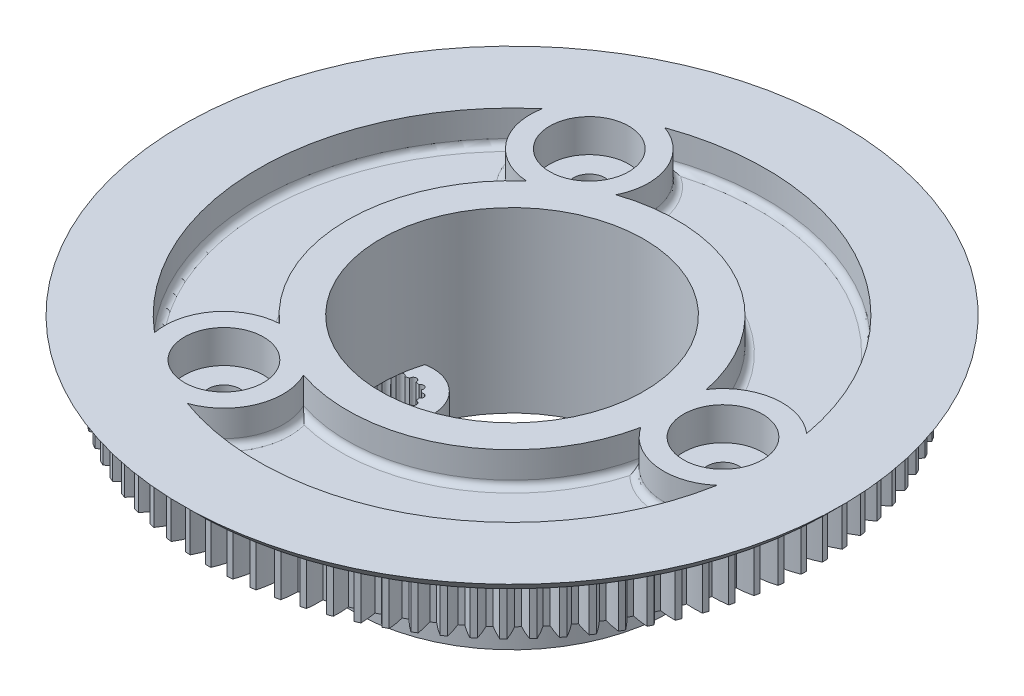
SolidWorks part; units mm, degrees
ref_plane "Plan de face" through (0, 0, 0) normal (0, 0, 1) x (1, 0, 0)
ref_plane "Plan de dessus" through (0, 0, 0) normal (0, 1, 0) x (1, 0, 0)
ref_plane "Plan de droite" through (0, 0, 0) normal (1, 0, 0) x (0, 0, -1)
sketch "Esquisse1" plane through (0, 0, 0) normal (0, 1, 0) x (1, 0, 0)
  arc A0 (22.9936, 0.5427) -> (22.9806, 0.9454) centre (0, 0) ccw
  arc A1 (22.8997, 2.1454) -> (22.8586, 2.5462) centre (0, 0) ccw
  arc A2 (22.6943, 3.7375) -> (22.6253, 4.1345) centre (0, 0) ccw
  arc A3 (22.3783, 5.3115) -> (22.2818, 5.7027) centre (0, 0) ccw
  arc A4 (21.9533, 6.8596) -> (21.8297, 7.2431) centre (0, 0) ccw
  arc A5 (21.4213, 8.3743) -> (21.2713, 8.7482) centre (0, 0) ccw
  arc A6 (20.7849, 9.8481) -> (20.6092, 10.2107) centre (0, 0) ccw
  arc A7 (20.0473, 11.274) -> (19.8468, 11.6235) centre (0, 0) ccw
  arc A8 (19.2121, 12.645) -> (18.9876, 12.9796) centre (0, 0) ccw
  arc A9 (18.2832, 13.9544) -> (18.0359, 14.2725) centre (0, 0) ccw
  arc A10 (17.2653, 15.1958) -> (16.9964, 15.4959) centre (0, 0) ccw
  arc A11 (16.1632, 16.3631) -> (15.8741, 16.6437) centre (0, 0) ccw
  arc A12 (14.9824, 17.4507) -> (14.6744, 17.7105) centre (0, 0) ccw
  arc A13 (13.7286, 18.4533) -> (13.4032, 18.691) centre (0, 0) ccw
  arc A14 (12.4079, 19.366) -> (12.0668, 19.5804) centre (0, 0) ccw
  arc A15 (11.0268, 20.1844) -> (10.6715, 20.3745) centre (0, 0) ccw
  arc A16 (9.5919, 20.9044) -> (9.2243, 21.0692) centre (0, 0) ccw
  arc A17 (8.1103, 21.5226) -> (7.7321, 21.6614) centre (0, 0) ccw
  arc A18 (6.5892, 22.0359) -> (6.2022, 22.148) centre (0, 0) ccw
  arc A19 (5.036, 22.4419) -> (4.6421, 22.5267) centre (0, 0) ccw
  arc A20 (3.4583, 22.7385) -> (3.0595, 22.7956) centre (0, 0) ccw
  arc A21 (1.8637, 22.9244) -> (1.4619, 22.9535) centre (0, 0) ccw
  arc A22 (0.2601, 22.9985) -> (-0.1429, 22.9996) centre (0, 0) ccw
  arc A23 (-1.3449, 22.9606) -> (-1.7469, 22.9336) centre (0, 0) ccw
  arc A24 (-2.9432, 22.8109) -> (-3.3424, 22.7558) centre (0, 0) ccw
  arc A25 (-4.5273, 22.55) -> (-4.9216, 22.4673) centre (0, 0) ccw
  arc A26 (-6.0893, 22.1793) -> (-6.4769, 22.0692) centre (0, 0) ccw
  arc A27 (-7.6216, 21.7005) -> (-8.0005, 21.5637) centre (0, 0) ccw
  arc A28 (-9.1168, 21.116) -> (-9.4853, 20.953) centre (0, 0) ccw
  arc A29 (-10.5675, 20.4286) -> (-10.9238, 20.2403) centre (0, 0) ccw
  arc A30 (-11.9668, 19.6417) -> (-12.3091, 19.429) centre (0, 0) ccw
  arc A31 (-13.3078, 18.7591) -> (-13.6344, 18.5231) centre (0, 0) ccw
  arc A32 (-14.584, 17.7851) -> (-14.8933, 17.5269) centre (0, 0) ccw
  arc A33 (-15.789, 16.7244) -> (-16.0796, 16.4453) centre (0, 0) ccw
  arc A34 (-16.9172, 15.5823) -> (-17.1876, 15.2835) centre (0, 0) ccw
  arc A35 (-17.963, 14.3642) -> (-18.2118, 14.0474) centre (0, 0) ccw
  arc A36 (-18.9212, 13.0762) -> (-19.1474, 12.7428) centre (0, 0) ccw
  arc A37 (-19.7873, 11.7245) -> (-19.9896, 11.3761) centre (0, 0) ccw
  arc A38 (-20.5569, 10.3156) -> (-20.7345, 9.9539) centre (0, 0) ccw
  arc A39 (-21.2264, 8.8565) -> (-21.3783, 8.4833) centre (0, 0) ccw
  arc A40 (-21.7925, 7.3543) -> (-21.918, 6.9714) centre (0, 0) ccw
  arc A41 (-22.2525, 5.8162) -> (-22.3509, 5.4255) centre (0, 0) ccw
  arc A42 (-22.604, 4.2498) -> (-22.6749, 3.8531) centre (0, 0) ccw
  arc A43 (-22.8454, 2.6626) -> (-22.8885, 2.262) centre (0, 0) ccw
  arc A44 (-22.9754, 1.0625) -> (-22.9905, 0.6599) centre (0, 0) ccw
  arc A45 (-22.9936, -0.5427) -> (-22.9806, -0.9454) centre (0, 0) ccw
  arc A46 (-22.8997, -2.1454) -> (-22.8586, -2.5462) centre (0, 0) ccw
  arc A47 (-22.6943, -3.7375) -> (-22.6253, -4.1345) centre (0, 0) ccw
  arc A48 (-22.3783, -5.3115) -> (-22.2818, -5.7027) centre (0, 0) ccw
  arc A49 (-21.9533, -6.8596) -> (-21.8297, -7.2431) centre (0, 0) ccw
  arc A50 (-21.4213, -8.3743) -> (-21.2713, -8.7482) centre (0, 0) ccw
  arc A51 (-20.7849, -9.8481) -> (-20.6092, -10.2107) centre (0, 0) ccw
  arc A52 (-20.0473, -11.274) -> (-19.8468, -11.6235) centre (0, 0) ccw
  arc A53 (-19.2121, -12.645) -> (-18.9876, -12.9796) centre (0, 0) ccw
  arc A54 (-18.2832, -13.9544) -> (-18.0359, -14.2725) centre (0, 0) ccw
  arc A55 (-17.2653, -15.1958) -> (-16.9964, -15.4959) centre (0, 0) ccw
  arc A56 (-16.1632, -16.3631) -> (-15.8741, -16.6437) centre (0, 0) ccw
  arc A57 (-14.9824, -17.4507) -> (-14.6744, -17.7105) centre (0, 0) ccw
  arc A58 (-13.7286, -18.4533) -> (-13.4032, -18.691) centre (0, 0) ccw
  arc A59 (-12.4079, -19.366) -> (-12.0668, -19.5804) centre (0, 0) ccw
  arc A60 (-11.0268, -20.1844) -> (-10.6715, -20.3745) centre (0, 0) ccw
  arc A61 (-9.5919, -20.9044) -> (-9.2243, -21.0692) centre (0, 0) ccw
  arc A62 (-8.1103, -21.5226) -> (-7.7321, -21.6614) centre (0, 0) ccw
  arc A63 (-6.5892, -22.0359) -> (-6.2022, -22.148) centre (0, 0) ccw
  arc A64 (-5.036, -22.4419) -> (-4.6421, -22.5267) centre (0, 0) ccw
  arc A65 (-3.4583, -22.7385) -> (-3.0595, -22.7956) centre (0, 0) ccw
  arc A66 (-1.8637, -22.9244) -> (-1.4619, -22.9535) centre (0, 0) ccw
  arc A67 (-0.2601, -22.9985) -> (0.1429, -22.9996) centre (0, 0) ccw
  arc A68 (1.3449, -22.9606) -> (1.7469, -22.9336) centre (0, 0) ccw
  arc A69 (2.9432, -22.8109) -> (3.3424, -22.7558) centre (0, 0) ccw
  arc A70 (4.5273, -22.55) -> (4.9216, -22.4673) centre (0, 0) ccw
  arc A71 (6.0893, -22.1793) -> (6.4769, -22.0692) centre (0, 0) ccw
  arc A72 (7.6216, -21.7005) -> (8.0005, -21.5637) centre (0, 0) ccw
  arc A73 (9.1168, -21.116) -> (9.4853, -20.953) centre (0, 0) ccw
  arc A74 (10.5675, -20.4286) -> (10.9238, -20.2403) centre (0, 0) ccw
  arc A75 (11.9668, -19.6417) -> (12.3091, -19.429) centre (0, 0) ccw
  arc A76 (13.3078, -18.7591) -> (13.6344, -18.5231) centre (0, 0) ccw
  arc A77 (14.584, -17.7851) -> (14.8933, -17.5269) centre (0, 0) ccw
  arc A78 (15.789, -16.7244) -> (16.0796, -16.4453) centre (0, 0) ccw
  arc A79 (16.9172, -15.5823) -> (17.1876, -15.2835) centre (0, 0) ccw
  arc A80 (17.963, -14.3642) -> (18.2118, -14.0474) centre (0, 0) ccw
  arc A81 (18.9212, -13.0762) -> (19.1474, -12.7428) centre (0, 0) ccw
  arc A82 (19.7873, -11.7245) -> (19.9896, -11.3761) centre (0, 0) ccw
  arc A83 (20.5569, -10.3156) -> (20.7345, -9.9539) centre (0, 0) ccw
  arc A84 (21.2264, -8.8565) -> (21.3783, -8.4833) centre (0, 0) ccw
  arc A85 (21.7925, -7.3543) -> (21.918, -6.9714) centre (0, 0) ccw
  arc A86 (22.2525, -5.8162) -> (22.3509, -5.4255) centre (0, 0) ccw
  arc A87 (22.604, -4.2498) -> (22.6749, -3.8531) centre (0, 0) ccw
  arc A88 (22.8454, -2.6626) -> (22.8885, -2.262) centre (0, 0) ccw
  arc A89 (22.9754, -1.0625) -> (22.9905, -0.6599) centre (0, 0) ccw
  arc A90 (21.8736, -0.2443) -> (21.8746, 0.1328) centre (0, 0) ccw
  arc A91 (21.8374, 1.2821) -> (21.812, 1.6584) centre (0, 0) ccw
  arc A92 (21.6948, 2.8023) -> (21.6432, 3.1759) centre (0, 0) ccw
  arc A93 (21.4464, 4.3088) -> (21.369, 4.6779) centre (0, 0) ccw
  arc A94 (21.0936, 5.7944) -> (20.9906, 6.1571) centre (0, 0) ccw
  arc A95 (20.638, 7.2517) -> (20.51, 7.6064) centre (0, 0) ccw
  arc A96 (20.0819, 8.6736) -> (19.9294, 9.0185) centre (0, 0) ccw
  arc A97 (19.428, 10.0533) -> (19.2518, 10.3868) centre (0, 0) ccw
  arc A98 (18.6794, 11.3841) -> (18.4803, 11.7044) centre (0, 0) ccw
  arc A99 (17.8397, 12.6594) -> (17.6189, 12.965) centre (0, 0) ccw
  arc A100 (16.9132, 13.873) -> (16.6715, 14.1625) centre (0, 0) ccw
  arc A101 (15.9043, 15.019) -> (15.643, 15.2909) centre (0, 0) ccw
  arc A102 (14.8179, 16.0918) -> (14.5383, 16.3449) centre (0, 0) ccw
  arc A103 (13.6593, 17.0863) -> (13.3627, 17.3192) centre (0, 0) ccw
  arc A104 (12.4341, 17.9975) -> (12.122, 18.2091) centre (0, 0) ccw
  arc A105 (11.1484, 18.821) -> (10.8223, 19.0104) centre (0, 0) ccw
  arc A106 (9.8083, 19.5528) -> (9.4698, 19.719) centre (0, 0) ccw
  arc A107 (8.4205, 20.1894) -> (8.0712, 20.3315) centre (0, 0) ccw
  arc A108 (6.9917, 20.7276) -> (6.6333, 20.845) centre (0, 0) ccw
  arc A109 (5.5288, 21.1648) -> (5.1631, 21.257) centre (0, 0) ccw
  arc A110 (4.0389, 21.4989) -> (3.6677, 21.5653) centre (0, 0) ccw
  arc A111 (2.5294, 21.7283) -> (2.1544, 21.7686) centre (0, 0) ccw
  arc A112 (1.0075, 21.8518) -> (0.6307, 21.8659) centre (0, 0) ccw
  arc A113 (-0.5192, 21.8688) -> (-0.8962, 21.8566) centre (0, 0) ccw
  arc A114 (-2.0435, 21.7793) -> (-2.4186, 21.7409) centre (0, 0) ccw
  arc A115 (-3.5577, 21.5837) -> (-3.9293, 21.5192) centre (0, 0) ccw
  arc A116 (-5.0547, 21.283) -> (-5.4208, 21.1927) centre (0, 0) ccw
  arc A117 (-6.527, 20.8786) -> (-6.8859, 20.7629) centre (0, 0) ccw
  arc A118 (-7.9675, 20.3724) -> (-8.3175, 20.232) centre (0, 0) ccw
  arc A119 (-9.3692, 19.767) -> (-9.7086, 19.6025) centre (0, 0) ccw
  arc A120 (-10.7252, 19.0653) -> (-11.0523, 18.8775) centre (0, 0) ccw
  arc A121 (-12.029, 18.2707) -> (-12.3422, 18.0606) centre (0, 0) ccw
  arc A122 (-13.2742, 17.3871) -> (-13.572, 17.1556) centre (0, 0) ccw
  arc A123 (-14.4548, 16.4187) -> (-14.7357, 16.1671) centre (0, 0) ccw
  arc A124 (-15.5649, 15.3704) -> (-15.8275, 15.0998) centre (0, 0) ccw
  arc A125 (-16.5991, 14.2472) -> (-16.8423, 13.959) centre (0, 0) ccw
  arc A126 (-17.5525, 13.0546) -> (-17.775, 12.7501) centre (0, 0) ccw
  arc A127 (-18.4204, 11.7984) -> (-18.6211, 11.4791) centre (0, 0) ccw
  arc A128 (-19.1986, 10.4848) -> (-19.3765, 10.1522) centre (0, 0) ccw
  arc A129 (-19.8832, 9.12) -> (-20.0375, 8.7759) centre (0, 0) ccw
  arc A130 (-20.4709, 7.7108) -> (-20.6008, 7.3567) centre (0, 0) ccw
  arc A131 (-20.959, 6.264) -> (-21.0638, 5.9018) centre (0, 0) ccw
  arc A132 (-21.3449, 4.7867) -> (-21.4242, 4.4181) centre (0, 0) ccw
  arc A133 (-21.6268, 3.2861) -> (-21.6802, 2.9128) centre (0, 0) ccw
  arc A134 (-21.8033, 1.7695) -> (-21.8306, 1.3934) centre (0, 0) ccw
  arc A135 (-21.8736, 0.2443) -> (-21.8746, -0.1328) centre (0, 0) ccw
  arc A136 (-21.8374, -1.2821) -> (-21.812, -1.6584) centre (0, 0) ccw
  arc A137 (-21.6948, -2.8023) -> (-21.6432, -3.1759) centre (0, 0) ccw
  arc A138 (-21.4464, -4.3088) -> (-21.369, -4.6779) centre (0, 0) ccw
  arc A139 (-21.0936, -5.7944) -> (-20.9906, -6.1571) centre (0, 0) ccw
  arc A140 (-20.638, -7.2517) -> (-20.51, -7.6064) centre (0, 0) ccw
  arc A141 (-20.0819, -8.6736) -> (-19.9294, -9.0185) centre (0, 0) ccw
  arc A142 (-19.428, -10.0533) -> (-19.2518, -10.3868) centre (0, 0) ccw
  arc A143 (-18.6794, -11.3841) -> (-18.4803, -11.7044) centre (0, 0) ccw
  arc A144 (-17.8397, -12.6594) -> (-17.6189, -12.965) centre (0, 0) ccw
  arc A145 (-16.9132, -13.873) -> (-16.6715, -14.1625) centre (0, 0) ccw
  arc A146 (-15.9043, -15.019) -> (-15.643, -15.2909) centre (0, 0) ccw
  arc A147 (-14.8179, -16.0918) -> (-14.5383, -16.3449) centre (0, 0) ccw
  arc A148 (-13.6593, -17.0863) -> (-13.3627, -17.3192) centre (0, 0) ccw
  arc A149 (-12.4341, -17.9975) -> (-12.122, -18.2091) centre (0, 0) ccw
  arc A150 (-11.1484, -18.821) -> (-10.8223, -19.0104) centre (0, 0) ccw
  arc A151 (-9.8083, -19.5528) -> (-9.4698, -19.719) centre (0, 0) ccw
  arc A152 (-8.4205, -20.1894) -> (-8.0712, -20.3315) centre (0, 0) ccw
  arc A153 (-6.9917, -20.7276) -> (-6.6333, -20.845) centre (0, 0) ccw
  arc A154 (-5.5288, -21.1648) -> (-5.1631, -21.257) centre (0, 0) ccw
  arc A155 (-4.0389, -21.4989) -> (-3.6677, -21.5653) centre (0, 0) ccw
  arc A156 (-2.5294, -21.7283) -> (-2.1544, -21.7686) centre (0, 0) ccw
  arc A157 (-1.0075, -21.8518) -> (-0.6307, -21.8659) centre (0, 0) ccw
  arc A158 (0.5192, -21.8688) -> (0.8962, -21.8566) centre (0, 0) ccw
  arc A159 (2.0435, -21.7793) -> (2.4186, -21.7409) centre (0, 0) ccw
  arc A160 (3.5577, -21.5837) -> (3.9293, -21.5192) centre (0, 0) ccw
  arc A161 (5.0547, -21.283) -> (5.4208, -21.1927) centre (0, 0) ccw
  arc A162 (6.527, -20.8786) -> (6.8859, -20.7629) centre (0, 0) ccw
  arc A163 (7.9675, -20.3724) -> (8.3175, -20.232) centre (0, 0) ccw
  arc A164 (9.3692, -19.767) -> (9.7086, -19.6025) centre (0, 0) ccw
  arc A165 (10.7252, -19.0653) -> (11.0523, -18.8775) centre (0, 0) ccw
  arc A166 (12.029, -18.2707) -> (12.3422, -18.0606) centre (0, 0) ccw
  arc A167 (13.2742, -17.3871) -> (13.572, -17.1556) centre (0, 0) ccw
  arc A168 (14.4548, -16.4187) -> (14.7357, -16.1671) centre (0, 0) ccw
  arc A169 (15.5649, -15.3704) -> (15.8275, -15.0998) centre (0, 0) ccw
  arc A170 (16.5991, -14.2472) -> (16.8423, -13.959) centre (0, 0) ccw
  arc A171 (17.5525, -13.0546) -> (17.775, -12.7501) centre (0, 0) ccw
  arc A172 (18.4204, -11.7984) -> (18.6211, -11.4791) centre (0, 0) ccw
  arc A173 (19.1986, -10.4848) -> (19.3765, -10.1522) centre (0, 0) ccw
  arc A174 (19.8832, -9.12) -> (20.0375, -8.7759) centre (0, 0) ccw
  arc A175 (20.4709, -7.7108) -> (20.6008, -7.3567) centre (0, 0) ccw
  arc A176 (20.959, -6.264) -> (21.0638, -5.9018) centre (0, 0) ccw
  arc A177 (21.3449, -4.7867) -> (21.4242, -4.4181) centre (0, 0) ccw
  arc A178 (21.6268, -3.2861) -> (21.6802, -2.9128) centre (0, 0) ccw
  arc A179 (21.8033, -1.7695) -> (21.8306, -1.3934) centre (0, 0) ccw
  circle A180 centre (0, 0) radius 10
  spline S0 degree 3 poles (21.8746, 0.1328) (22.0856, 0.1898) (22.4638, 0.3142) (22.8305, 0.4682) (22.9936, 0.5427) knots 0.743744 0.743744 0.743744 0.743744 1.398733 1.936502 1.936502 1.936502 1.936502
  spline S1 degree 3 poles (21.8374, 1.2821) (22.0517, 1.2389) (22.4371, 1.1392) (22.8129, 1.0092) (22.9806, 0.9454) knots 0.743744 0.743744 0.743744 0.743744 1.398733 1.936502 1.936502 1.936502 1.936502
  spline S2 degree 3 poles (21.812, 1.6584) (22.0186, 1.73) (22.3872, 1.8804) (22.7422, 2.0596) (22.8997, 2.1454) knots 0.743744 0.743744 0.743744 0.743744 1.398733 1.936502 1.936502 1.936502 1.936502
  spline S3 degree 3 poles (21.6948, 2.8023) (21.9115, 2.7741) (22.303, 2.7016) (22.687, 2.5981) (22.8586, 2.5462) knots 0.743744 0.743744 0.743744 0.743744 1.398733 1.936502 1.936502 1.936502 1.936502
  spline S4 degree 3 poles (21.6432, 3.1759) (21.8443, 3.2617) (22.2015, 3.4375) (22.5431, 3.641) (22.6943, 3.7375) knots 0.743744 0.743744 0.743744 0.743744 1.398733 1.936502 1.936502 1.936502 1.936502
  spline S5 degree 3 poles (21.4464, 4.3088) (21.6646, 4.2958) (22.0602, 4.2508) (22.4505, 4.1744) (22.6253, 4.1345) knots 0.743744 0.743744 0.743744 0.743744 1.398733 1.936502 1.936502 1.936502 1.936502
  spline S6 degree 3 poles (21.369, 4.6779) (21.5635, 4.7775) (21.9076, 4.9778) (22.2342, 5.2047) (22.3783, 5.3115) knots 0.743744 0.743744 0.743744 0.743744 1.398733 1.936502 1.936502 1.936502 1.936502
  spline S7 degree 3 poles (21.0936, 5.7944) (21.3122, 5.7966) (21.7099, 5.7793) (22.1046, 5.7303) (22.2818, 5.7027) knots 0.743744 0.743744 0.743744 0.743744 1.398733 1.936502 1.936502 1.936502 1.936502
  spline S8 degree 3 poles (20.9906, 6.1571) (21.1777, 6.2701) (21.507, 6.4939) (21.817, 6.743) (21.9533, 6.8596) knots 0.743744 0.743744 0.743744 0.743744 1.398733 1.936502 1.936502 1.936502 1.936502
  spline S9 degree 3 poles (20.638, 7.2517) (20.8559, 7.2692) (21.2539, 7.2796) (21.651, 7.2583) (21.8297, 7.2431) knots 0.743744 0.743744 0.743744 0.743744 1.398733 1.936502 1.936502 1.936502 1.936502
  spline S10 degree 3 poles (20.51, 7.6064) (20.6888, 7.7321) (21.0016, 7.9783) (21.2935, 8.2485) (21.4213, 8.3743) knots 0.743744 0.743744 0.743744 0.743744 1.398733 1.936502 1.936502 1.936502 1.936502
  spline S11 degree 3 poles (20.0819, 8.6736) (20.2981, 8.7063) (20.6943, 8.7445) (21.092, 8.7509) (21.2713, 8.7482) knots 0.743744 0.743744 0.743744 0.743744 1.398733 1.936502 1.936502 1.936502 1.936502
  spline S12 degree 3 poles (19.9294, 9.0185) (20.099, 9.1564) (20.3939, 9.4239) (20.6662, 9.7137) (20.7849, 9.8481) knots 0.743744 0.743744 0.743744 0.743744 1.398733 1.936502 1.936502 1.936502 1.936502
  spline S13 degree 3 poles (19.428, 10.0533) (19.6413, 10.101) (20.0339, 10.1667) (20.4302, 10.2009) (20.6092, 10.2107) knots 0.743744 0.743744 0.743744 0.743744 1.398733 1.936502 1.936502 1.936502 1.936502
  spline S14 degree 3 poles (19.2518, 10.3868) (19.4113, 10.5362) (19.6869, 10.8235) (19.9383, 11.1317) (20.0473, 11.274) knots 0.743744 0.743744 0.743744 0.743744 1.398733 1.936502 1.936502 1.936502 1.936502
  spline S15 degree 3 poles (18.6794, 11.3841) (18.8888, 11.4465) (19.2759, 11.5395) (19.6688, 11.6011) (19.8468, 11.6235) knots 0.743744 0.743744 0.743744 0.743744 1.398733 1.936502 1.936502 1.936502 1.936502
  spline S16 degree 3 poles (18.4803, 11.7044) (18.6291, 11.8646) (18.8839, 12.1705) (19.1132, 12.4954) (19.2121, 12.645) knots 0.743744 0.743744 0.743744 0.743744 1.398733 1.936502 1.936502 1.936502 1.936502
  spline S17 degree 3 poles (17.8397, 12.6594) (18.0444, 12.7362) (18.424, 12.856) (18.8117, 12.9449) (18.9876, 12.9796) knots 0.743744 0.743744 0.743744 0.743744 1.398733 1.936502 1.936502 1.936502 1.936502
  spline S18 degree 3 poles (17.6189, 12.965) (17.7561, 13.1352) (17.9889, 13.4581) (18.195, 13.7982) (18.2832, 13.9544) knots 0.743744 0.743744 0.743744 0.743744 1.398733 1.936502 1.936502 1.936502 1.936502
  spline S19 degree 3 poles (16.9132, 13.873) (17.112, 13.9639) (17.4824, 14.1099) (17.8628, 14.2256) (18.0359, 14.2725) knots 0.743744 0.743744 0.743744 0.743744 1.398733 1.936502 1.936502 1.936502 1.936502
  spline S20 degree 3 poles (16.6715, 14.1625) (16.7966, 14.3418) (17.0063, 14.6801) (17.1882, 15.0338) (17.2653, 15.1958) knots 0.743744 0.743744 0.743744 0.743744 1.398733 1.936502 1.936502 1.936502 1.936502
  spline S21 degree 3 poles (15.9043, 15.019) (16.0962, 15.1236) (16.4555, 15.295) (16.827, 15.437) (16.9964, 15.4959) knots 0.743744 0.743744 0.743744 0.743744 1.398733 1.936502 1.936502 1.936502 1.936502
  spline S22 degree 3 poles (15.643, 15.2909) (15.7552, 15.4785) (15.9409, 15.8307) (16.0976, 16.1962) (16.1632, 16.3631) knots 0.743744 0.743744 0.743744 0.743744 1.398733 1.936502 1.936502 1.936502 1.936502
  spline S23 degree 3 poles (14.8179, 16.0918) (15.002, 16.2096) (15.3485, 16.4056) (15.7092, 16.5732) (15.8741, 16.6437) knots 0.743744 0.743744 0.743744 0.743744 1.398733 1.936502 1.936502 1.936502 1.936502
  spline S24 degree 3 poles (14.5383, 16.3449) (14.6371, 16.5398) (14.7977, 16.9041) (14.9286, 17.2796) (14.9824, 17.4507) knots 0.743744 0.743744 0.743744 0.743744 1.398733 1.936502 1.936502 1.936502 1.936502
  spline S25 degree 3 poles (13.6593, 17.0863) (13.8348, 17.2166) (14.1667, 17.4363) (14.5148, 17.6286) (14.6744, 17.7105) knots 0.743744 0.743744 0.743744 0.743744 1.398733 1.936502 1.936502 1.936502 1.936502
  spline S26 degree 3 poles (13.3627, 17.3192) (13.4477, 17.5206) (13.5825, 17.8952) (13.6869, 18.2789) (13.7286, 18.4533) knots 0.743744 0.743744 0.743744 0.743744 1.398733 1.936502 1.936502 1.936502 1.936502
  spline S27 degree 3 poles (12.4341, 17.9975) (12.6001, 18.1397) (12.9159, 18.3821) (13.2498, 18.5982) (13.4032, 18.691) knots 0.743744 0.743744 0.743744 0.743744 1.398733 1.936502 1.936502 1.936502 1.936502
  spline S28 degree 3 poles (12.122, 18.2091) (12.1928, 18.416) (12.3011, 18.799) (12.3785, 19.1891) (12.4079, 19.366) knots 0.743744 0.743744 0.743744 0.743744 1.398733 1.936502 1.936502 1.936502 1.936502
  spline S29 degree 3 poles (11.1484, 18.821) (11.304, 18.9744) (11.6022, 19.2383) (11.9201, 19.4772) (12.0668, 19.5804) knots 0.743744 0.743744 0.743744 0.743744 1.398733 1.936502 1.936502 1.936502 1.936502
  spline S30 degree 3 poles (10.8223, 19.0104) (10.8784, 19.2216) (10.9598, 19.6113) (11.0097, 20.0059) (11.0268, 20.1844) knots 0.743744 0.743744 0.743744 0.743744 1.398733 1.936502 1.936502 1.936502 1.936502
  spline S31 degree 3 poles (9.8083, 19.5528) (9.9529, 19.7168) (10.2319, 20.0007) (10.5324, 20.2612) (10.6715, 20.3745) knots 0.743744 0.743744 0.743744 0.743744 1.398733 1.936502 1.936502 1.936502 1.936502
  spline S32 degree 3 poles (9.4698, 19.719) (9.5111, 19.9336) (9.5651, 20.3281) (9.5874, 20.7251) (9.5919, 20.9044) knots 0.743744 0.743744 0.743744 0.743744 1.398733 1.936502 1.936502 1.936502 1.936502
  spline S33 degree 3 poles (8.4205, 20.1894) (8.5533, 20.363) (8.8118, 20.6658) (9.0934, 20.9466) (9.2243, 21.0692) knots 0.743744 0.743744 0.743744 0.743744 1.398733 1.936502 1.936502 1.936502 1.936502
  spline S34 degree 3 poles (8.0712, 20.3315) (8.0974, 20.5485) (8.1238, 20.9458) (8.1183, 21.3434) (8.1103, 21.5226) knots 0.743744 0.743744 0.743744 0.743744 1.398733 1.936502 1.936502 1.936502 1.936502
  spline S35 degree 3 poles (6.9917, 20.7276) (7.112, 20.9101) (7.3488, 21.2301) (7.6101, 21.5299) (7.7321, 21.6614) knots 0.743744 0.743744 0.743744 0.743744 1.398733 1.936502 1.936502 1.936502 1.936502
  spline S36 degree 3 poles (6.6333, 20.845) (6.6443, 21.0633) (6.6429, 21.4614) (6.6097, 21.8577) (6.5892, 22.0359) knots 0.743744 0.743744 0.743744 0.743744 1.398733 1.936502 1.936502 1.936502 1.936502
  spline S37 degree 3 poles (5.5288, 21.1648) (5.6361, 21.3552) (5.85, 21.691) (6.0897, 22.0083) (6.2022, 22.148) knots 0.743744 0.743744 0.743744 0.743744 1.398733 1.936502 1.936502 1.936502 1.936502
  spline S38 degree 3 poles (5.1631, 21.257) (5.1588, 21.4755) (5.1296, 21.8726) (5.0689, 22.2656) (5.036, 22.4419) knots 0.743744 0.743744 0.743744 0.743744 1.398733 1.936502 1.936502 1.936502 1.936502
  spline S39 degree 3 poles (4.0389, 21.4989) (4.1327, 21.6964) (4.3226, 22.0462) (4.5397, 22.3795) (4.6421, 22.5267) knots 0.743744 0.743744 0.743744 0.743744 1.398733 1.936502 1.936502 1.936502 1.936502
  spline S40 degree 3 poles (3.6677, 21.5653) (3.6482, 21.7831) (3.5914, 22.1771) (3.5034, 22.5649) (3.4583, 22.7385) knots 0.743744 0.743744 0.743744 0.743744 1.398733 1.936502 1.936502 1.936502 1.936502
  spline S41 degree 3 poles (2.5294, 21.7283) (2.6092, 21.9318) (2.7742, 22.2941) (2.9675, 22.6416) (3.0595, 22.7956) knots 0.743744 0.743744 0.743744 0.743744 1.398733 1.936502 1.936502 1.936502 1.936502
  spline S42 degree 3 poles (2.1544, 21.7686) (2.1198, 21.9845) (2.0356, 22.3736) (1.9208, 22.7543) (1.8637, 22.9244) knots 0.743744 0.743744 0.743744 0.743744 1.398733 1.936502 1.936502 1.936502 1.936502
  spline S43 degree 3 poles (1.0075, 21.8518) (1.0729, 22.0604) (1.2123, 22.4333) (1.3809, 22.7935) (1.4619, 22.9535) knots 0.743744 0.743744 0.743744 0.743744 1.398733 1.936502 1.936502 1.936502 1.936502
  spline S44 degree 3 poles (0.6307, 21.8659) (0.5811, 22.0788) (0.47, 22.4611) (0.3288, 22.8329) (0.2601, 22.9985) knots 0.743744 0.743744 0.743744 0.743744 1.398733 1.936502 1.936502 1.936502 1.936502
  spline S45 degree 3 poles (-0.5192, 21.8688) (-0.4685, 22.0815) (-0.3555, 22.4632) (-0.2125, 22.8343) (-0.1429, 22.9996) knots 0.743744 0.743744 0.743744 0.743744 1.398733 1.936502 1.936502 1.936502 1.936502
  spline S46 degree 3 poles (-0.8962, 21.8566) (-0.9605, 22.0655) (-1.098, 22.4392) (-1.2647, 22.8002) (-1.3449, 22.9606) knots 0.743744 0.743744 0.743744 0.743744 1.398733 1.936502 1.936502 1.936502 1.936502
  spline S47 degree 3 poles (-2.0435, 21.7793) (-2.0077, 21.995) (-1.9216, 22.3837) (-1.8048, 22.7638) (-1.7469, 22.9336) knots 0.743744 0.743744 0.743744 0.743744 1.398733 1.936502 1.936502 1.936502 1.936502
  spline S48 degree 3 poles (-2.4186, 21.7409) (-2.4974, 21.9448) (-2.6606, 22.3079) (-2.8521, 22.6564) (-2.9432, 22.8109) knots 0.743744 0.743744 0.743744 0.743744 1.398733 1.936502 1.936502 1.936502 1.936502
  spline S49 degree 3 poles (-3.5577, 21.5837) (-3.5371, 21.8014) (-3.4783, 22.1951) (-3.3883, 22.5825) (-3.3424, 22.7558) knots 0.743744 0.743744 0.743744 0.743744 1.398733 1.936502 1.936502 1.936502 1.936502
  spline S50 degree 3 poles (-3.9293, 21.5192) (-4.0221, 21.7171) (-4.2102, 22.068) (-4.4256, 22.4023) (-4.5273, 22.55) knots 0.743744 0.743744 0.743744 0.743744 1.398733 1.936502 1.936502 1.936502 1.936502
  spline S51 degree 3 poles (-5.0547, 21.283) (-5.0493, 21.5015) (-5.0181, 21.8984) (-4.9553, 22.2911) (-4.9216, 22.4673) knots 0.743744 0.743744 0.743744 0.743744 1.398733 1.936502 1.936502 1.936502 1.936502
  spline S52 degree 3 poles (-5.4208, 21.1927) (-5.5272, 21.3837) (-5.7393, 21.7205) (-5.9775, 22.039) (-6.0893, 22.1793) knots 0.743744 0.743744 0.743744 0.743744 1.398733 1.936502 1.936502 1.936502 1.936502
  spline S53 degree 3 poles (-6.527, 20.8786) (-6.5369, 21.0969) (-6.5334, 21.495) (-6.4982, 21.8911) (-6.4769, 22.0692) knots 0.743744 0.743744 0.743744 0.743744 1.398733 1.936502 1.936502 1.936502 1.936502
  spline S54 degree 3 poles (-6.8859, 20.7629) (-7.0054, 20.946) (-7.2405, 21.2673) (-7.5003, 21.5684) (-7.6216, 21.7005) knots 0.743744 0.743744 0.743744 0.743744 1.398733 1.936502 1.936502 1.936502 1.936502
  spline S55 degree 3 poles (-7.9675, 20.3724) (-7.9926, 20.5895) (-8.0169, 20.9869) (-8.0094, 21.3845) (-8.0005, 21.5637) knots 0.743744 0.743744 0.743744 0.743744 1.398733 1.936502 1.936502 1.936502 1.936502
  spline S56 degree 3 poles (-8.3175, 20.232) (-8.4494, 20.4063) (-8.7064, 20.7104) (-8.9866, 20.9926) (-9.1168, 21.116) knots 0.743744 0.743744 0.743744 0.743744 1.398733 1.936502 1.936502 1.936502 1.936502
  spline S57 degree 3 poles (-9.3692, 19.767) (-9.4094, 19.9819) (-9.4614, 20.3766) (-9.4816, 20.7737) (-9.4853, 20.953) knots 0.743744 0.743744 0.743744 0.743744 1.398733 1.936502 1.936502 1.936502 1.936502
  spline S58 degree 3 poles (-9.7086, 19.6025) (-9.8523, 19.7672) (-10.1299, 20.0526) (-10.429, 20.3146) (-10.5675, 20.4286) knots 0.743744 0.743744 0.743744 0.743744 1.398733 1.936502 1.936502 1.936502 1.936502
  spline S59 degree 3 poles (-10.7252, 19.0653) (-10.7803, 19.2768) (-10.8597, 19.6669) (-10.9076, 20.0617) (-10.9238, 20.2403) knots 0.743744 0.743744 0.743744 0.743744 1.398733 1.936502 1.936502 1.936502 1.936502
  spline S60 degree 3 poles (-11.0523, 18.8775) (-11.2072, 19.0318) (-11.504, 19.2971) (-11.8207, 19.5377) (-11.9668, 19.6417) knots 0.743744 0.743744 0.743744 0.743744 1.398733 1.936502 1.936502 1.936502 1.936502
  spline S61 degree 3 poles (-12.029, 18.2707) (-12.0987, 18.4779) (-12.2052, 18.8615) (-12.2805, 19.252) (-12.3091, 19.429) knots 0.743744 0.743744 0.743744 0.743744 1.398733 1.936502 1.936502 1.936502 1.936502
  spline S62 degree 3 poles (-12.3422, 18.0606) (-12.5075, 18.2037) (-12.8221, 18.4477) (-13.1548, 18.6655) (-13.3078, 18.7591) knots 0.743744 0.743744 0.743744 0.743744 1.398733 1.936502 1.936502 1.936502 1.936502
  spline S63 degree 3 poles (-13.2742, 17.3871) (-13.3582, 17.5889) (-13.4911, 17.9641) (-13.5935, 18.3484) (-13.6344, 18.5231) knots 0.743744 0.743744 0.743744 0.743744 1.398733 1.936502 1.936502 1.936502 1.936502
  spline S64 degree 3 poles (-13.572, 17.1556) (-13.7468, 17.2868) (-14.0777, 17.5083) (-14.4248, 17.7024) (-14.584, 17.7851) knots 0.743744 0.743744 0.743744 0.743744 1.398733 1.936502 1.936502 1.936502 1.936502
  spline S65 degree 3 poles (-14.4548, 16.4187) (-14.5526, 16.6142) (-14.7114, 16.9793) (-14.8404, 17.3555) (-14.8933, 17.5269) knots 0.743744 0.743744 0.743744 0.743744 1.398733 1.936502 1.936502 1.936502 1.936502
  spline S66 degree 3 poles (-14.7357, 16.1671) (-14.9192, 16.2858) (-15.2647, 16.4836) (-15.6245, 16.653) (-15.789, 16.7244) knots 0.743744 0.743744 0.743744 0.743744 1.398733 1.936502 1.936502 1.936502 1.936502
  spline S67 degree 3 poles (-15.5649, 15.3704) (-15.6761, 15.5586) (-15.86, 15.9117) (-16.0149, 16.278) (-16.0796, 16.4453) knots 0.743744 0.743744 0.743744 0.743744 1.398733 1.936502 1.936502 1.936502 1.936502
  spline S68 degree 3 poles (-15.8275, 15.0998) (-16.0189, 15.2054) (-16.3774, 15.3787) (-16.7481, 15.5226) (-16.9172, 15.5823) knots 0.743744 0.743744 0.743744 0.743744 1.398733 1.936502 1.936502 1.936502 1.936502
  spline S69 degree 3 poles (-16.5991, 14.2472) (-16.7233, 14.4272) (-16.9313, 14.7666) (-17.1113, 15.1212) (-17.1876, 15.2835) knots 0.743744 0.743744 0.743744 0.743744 1.398733 1.936502 1.936502 1.936502 1.936502
  spline S70 degree 3 poles (-16.8423, 13.959) (-17.0406, 14.051) (-17.4102, 14.1988) (-17.7901, 14.3165) (-17.963, 14.3642) knots 0.743744 0.743744 0.743744 0.743744 1.398733 1.936502 1.936502 1.936502 1.936502
  spline S71 degree 3 poles (-17.5525, 13.0546) (-17.6889, 13.2255) (-17.9201, 13.5496) (-18.1245, 13.8907) (-18.2118, 14.0474) knots 0.743744 0.743744 0.743744 0.743744 1.398733 1.936502 1.936502 1.936502 1.936502
  spline S72 degree 3 poles (-17.775, 12.7501) (-17.9792, 12.828) (-18.3583, 12.9497) (-18.7454, 13.0406) (-18.9212, 13.0762) knots 0.743744 0.743744 0.743744 0.743744 1.398733 1.936502 1.936502 1.936502 1.936502
  spline S73 degree 3 poles (-18.4204, 11.7984) (-18.5684, 11.9594) (-18.8216, 12.2665) (-19.0493, 12.5926) (-19.1474, 12.7428) knots 0.743744 0.743744 0.743744 0.743744 1.398733 1.936502 1.936502 1.936502 1.936502
  spline S74 degree 3 poles (-18.6211, 11.4791) (-18.8303, 11.5426) (-19.2169, 11.6376) (-19.6094, 11.7012) (-19.7873, 11.7245) knots 0.743744 0.743744 0.743744 0.743744 1.398733 1.936502 1.936502 1.936502 1.936502
  spline S75 degree 3 poles (-19.1986, 10.4848) (-19.3574, 10.635) (-19.6315, 10.9237) (-19.8813, 11.2331) (-19.9896, 11.3761) knots 0.743744 0.743744 0.743744 0.743744 1.398733 1.936502 1.936502 1.936502 1.936502
  spline S76 degree 3 poles (-19.3765, 10.1522) (-19.5896, 10.201) (-19.9819, 10.2687) (-20.3779, 10.3048) (-20.5569, 10.3156) knots 0.743744 0.743744 0.743744 0.743744 1.398733 1.936502 1.936502 1.936502 1.936502
  spline S77 degree 3 poles (-19.8832, 9.12) (-20.0521, 9.2588) (-20.3456, 9.5277) (-20.6164, 9.8189) (-20.7345, 9.9539) knots 0.743744 0.743744 0.743744 0.743744 1.398733 1.936502 1.936502 1.936502 1.936502
  spline S78 degree 3 poles (-20.0375, 8.7759) (-20.2534, 8.8096) (-20.6495, 8.8498) (-21.0471, 8.8582) (-21.2264, 8.8565) knots 0.743744 0.743744 0.743744 0.743744 1.398733 1.936502 1.936502 1.936502 1.936502
  spline S79 degree 3 poles (-20.4709, 7.7108) (-20.6491, 7.8374) (-20.9607, 8.0852) (-21.2512, 8.3569) (-21.3783, 8.4833) knots 0.743744 0.743744 0.743744 0.743744 1.398733 1.936502 1.936502 1.936502 1.936502
  spline S80 degree 3 poles (-20.6008, 7.3567) (-20.8186, 7.3754) (-21.2165, 7.3878) (-21.6138, 7.3685) (-21.7925, 7.3543) knots 0.743744 0.743744 0.743744 0.743744 1.398733 1.936502 1.936502 1.936502 1.936502
  spline S81 degree 3 poles (-20.959, 6.264) (-21.1455, 6.3779) (-21.4736, 6.6034) (-21.7823, 6.8541) (-21.918, 6.9714) knots 0.743744 0.743744 0.743744 0.743744 1.398733 1.936502 1.936502 1.936502 1.936502
  spline S82 degree 3 poles (-21.0638, 5.9018) (-21.2824, 5.9052) (-21.6802, 5.8899) (-22.0751, 5.8429) (-22.2525, 5.8162) knots 0.743744 0.743744 0.743744 0.743744 1.398733 1.936502 1.936502 1.936502 1.936502
  spline S83 degree 3 poles (-21.3449, 4.7867) (-21.5389, 4.8874) (-21.882, 5.0894) (-22.2074, 5.3179) (-22.3509, 5.4255) knots 0.743744 0.743744 0.743744 0.743744 1.398733 1.936502 1.936502 1.936502 1.936502
  spline S84 degree 3 poles (-21.4242, 4.4181) (-21.6425, 4.4062) (-22.0382, 4.3632) (-22.4289, 4.2887) (-22.604, 4.2498) knots 0.743744 0.743744 0.743744 0.743744 1.398733 1.936502 1.936502 1.936502 1.936502
  spline S85 degree 3 poles (-21.6268, 3.2861) (-21.8274, 3.373) (-22.1837, 3.5506) (-22.5243, 3.7559) (-22.6749, 3.8531) knots 0.743744 0.743744 0.743744 0.743744 1.398733 1.936502 1.936502 1.936502 1.936502
  spline S86 degree 3 poles (-21.6802, 2.9128) (-21.8971, 2.8858) (-22.2889, 2.8152) (-22.6734, 2.7137) (-22.8454, 2.6626) knots 0.743744 0.743744 0.743744 0.743744 1.398733 1.936502 1.936502 1.936502 1.936502
  spline S87 degree 3 poles (-21.8033, 1.7695) (-22.0095, 1.8422) (-22.3773, 1.9945) (-22.7314, 2.1755) (-22.8885, 2.262) knots 0.743744 0.743744 0.743744 0.743744 1.398733 1.936502 1.936502 1.936502 1.936502
  spline S88 degree 3 poles (-21.8306, 1.3934) (-22.0451, 1.3513) (-22.431, 1.2536) (-22.8075, 1.1255) (-22.9754, 1.0625) knots 0.743744 0.743744 0.743744 0.743744 1.398733 1.936502 1.936502 1.936502 1.936502
  spline S89 degree 3 poles (-21.8736, 0.2443) (-22.0844, 0.3024) (-22.4619, 0.4287) (-22.8278, 0.5846) (-22.9905, 0.6599) knots 0.743744 0.743744 0.743744 0.743744 1.398733 1.936502 1.936502 1.936502 1.936502
  spline S90 degree 3 poles (-21.8746, -0.1328) (-22.0856, -0.1898) (-22.4638, -0.3142) (-22.8305, -0.4682) (-22.9936, -0.5427) knots 0.743744 0.743744 0.743744 0.743744 1.398733 1.936502 1.936502 1.936502 1.936502
  spline S91 degree 3 poles (-21.8374, -1.2821) (-22.0517, -1.2389) (-22.4371, -1.1392) (-22.8129, -1.0092) (-22.9806, -0.9454) knots 0.743744 0.743744 0.743744 0.743744 1.398733 1.936502 1.936502 1.936502 1.936502
  spline S92 degree 3 poles (-21.812, -1.6584) (-22.0186, -1.73) (-22.3872, -1.8804) (-22.7422, -2.0596) (-22.8997, -2.1454) knots 0.743744 0.743744 0.743744 0.743744 1.398733 1.936502 1.936502 1.936502 1.936502
  spline S93 degree 3 poles (-21.6948, -2.8023) (-21.9115, -2.7741) (-22.303, -2.7016) (-22.687, -2.5981) (-22.8586, -2.5462) knots 0.743744 0.743744 0.743744 0.743744 1.398733 1.936502 1.936502 1.936502 1.936502
  spline S94 degree 3 poles (-21.6432, -3.1759) (-21.8443, -3.2617) (-22.2015, -3.4375) (-22.5431, -3.641) (-22.6943, -3.7375) knots 0.743744 0.743744 0.743744 0.743744 1.398733 1.936502 1.936502 1.936502 1.936502
  spline S95 degree 3 poles (-21.4464, -4.3088) (-21.6646, -4.2958) (-22.0602, -4.2508) (-22.4505, -4.1744) (-22.6253, -4.1345) knots 0.743744 0.743744 0.743744 0.743744 1.398733 1.936502 1.936502 1.936502 1.936502
  spline S96 degree 3 poles (-21.369, -4.6779) (-21.5635, -4.7775) (-21.9076, -4.9778) (-22.2342, -5.2047) (-22.3783, -5.3115) knots 0.743744 0.743744 0.743744 0.743744 1.398733 1.936502 1.936502 1.936502 1.936502
  spline S97 degree 3 poles (-21.0936, -5.7944) (-21.3122, -5.7966) (-21.7099, -5.7793) (-22.1046, -5.7303) (-22.2818, -5.7027) knots 0.743744 0.743744 0.743744 0.743744 1.398733 1.936502 1.936502 1.936502 1.936502
  spline S98 degree 3 poles (-20.9906, -6.1571) (-21.1777, -6.2701) (-21.507, -6.4939) (-21.817, -6.743) (-21.9533, -6.8596) knots 0.743744 0.743744 0.743744 0.743744 1.398733 1.936502 1.936502 1.936502 1.936502
  spline S99 degree 3 poles (-20.638, -7.2517) (-20.8559, -7.2692) (-21.2539, -7.2796) (-21.651, -7.2583) (-21.8297, -7.2431) knots 0.743744 0.743744 0.743744 0.743744 1.398733 1.936502 1.936502 1.936502 1.936502
  spline S100 degree 3 poles (-20.51, -7.6064) (-20.6888, -7.7321) (-21.0016, -7.9783) (-21.2935, -8.2485) (-21.4213, -8.3743) knots 0.743744 0.743744 0.743744 0.743744 1.398733 1.936502 1.936502 1.936502 1.936502
  spline S101 degree 3 poles (-20.0819, -8.6736) (-20.2981, -8.7063) (-20.6943, -8.7445) (-21.092, -8.7509) (-21.2713, -8.7482) knots 0.743744 0.743744 0.743744 0.743744 1.398733 1.936502 1.936502 1.936502 1.936502
  spline S102 degree 3 poles (-19.9294, -9.0185) (-20.099, -9.1564) (-20.3939, -9.4239) (-20.6662, -9.7137) (-20.7849, -9.8481) knots 0.743744 0.743744 0.743744 0.743744 1.398733 1.936502 1.936502 1.936502 1.936502
  spline S103 degree 3 poles (-19.428, -10.0533) (-19.6413, -10.101) (-20.0339, -10.1667) (-20.4302, -10.2009) (-20.6092, -10.2107) knots 0.743744 0.743744 0.743744 0.743744 1.398733 1.936502 1.936502 1.936502 1.936502
  spline S104 degree 3 poles (-19.2518, -10.3868) (-19.4113, -10.5362) (-19.6869, -10.8235) (-19.9383, -11.1317) (-20.0473, -11.274) knots 0.743744 0.743744 0.743744 0.743744 1.398733 1.936502 1.936502 1.936502 1.936502
  spline S105 degree 3 poles (-18.6794, -11.3841) (-18.8888, -11.4465) (-19.2759, -11.5395) (-19.6688, -11.6011) (-19.8468, -11.6235) knots 0.743744 0.743744 0.743744 0.743744 1.398733 1.936502 1.936502 1.936502 1.936502
  spline S106 degree 3 poles (-18.4803, -11.7044) (-18.6291, -11.8646) (-18.8839, -12.1705) (-19.1132, -12.4954) (-19.2121, -12.645) knots 0.743744 0.743744 0.743744 0.743744 1.398733 1.936502 1.936502 1.936502 1.936502
  spline S107 degree 3 poles (-17.8397, -12.6594) (-18.0444, -12.7362) (-18.424, -12.856) (-18.8117, -12.9449) (-18.9876, -12.9796) knots 0.743744 0.743744 0.743744 0.743744 1.398733 1.936502 1.936502 1.936502 1.936502
  spline S108 degree 3 poles (-17.6189, -12.965) (-17.7561, -13.1352) (-17.9889, -13.4581) (-18.195, -13.7982) (-18.2832, -13.9544) knots 0.743744 0.743744 0.743744 0.743744 1.398733 1.936502 1.936502 1.936502 1.936502
  spline S109 degree 3 poles (-16.9132, -13.873) (-17.112, -13.9639) (-17.4824, -14.1099) (-17.8628, -14.2256) (-18.0359, -14.2725) knots 0.743744 0.743744 0.743744 0.743744 1.398733 1.936502 1.936502 1.936502 1.936502
  spline S110 degree 3 poles (-16.6715, -14.1625) (-16.7966, -14.3418) (-17.0063, -14.6801) (-17.1882, -15.0338) (-17.2653, -15.1958) knots 0.743744 0.743744 0.743744 0.743744 1.398733 1.936502 1.936502 1.936502 1.936502
  spline S111 degree 3 poles (-15.9043, -15.019) (-16.0962, -15.1236) (-16.4555, -15.295) (-16.827, -15.437) (-16.9964, -15.4959) knots 0.743744 0.743744 0.743744 0.743744 1.398733 1.936502 1.936502 1.936502 1.936502
  spline S112 degree 3 poles (-15.643, -15.2909) (-15.7552, -15.4785) (-15.9409, -15.8307) (-16.0976, -16.1962) (-16.1632, -16.3631) knots 0.743744 0.743744 0.743744 0.743744 1.398733 1.936502 1.936502 1.936502 1.936502
  spline S113 degree 3 poles (-14.8179, -16.0918) (-15.002, -16.2096) (-15.3485, -16.4056) (-15.7092, -16.5732) (-15.8741, -16.6437) knots 0.743744 0.743744 0.743744 0.743744 1.398733 1.936502 1.936502 1.936502 1.936502
  spline S114 degree 3 poles (-14.5383, -16.3449) (-14.6371, -16.5398) (-14.7977, -16.9041) (-14.9286, -17.2796) (-14.9824, -17.4507) knots 0.743744 0.743744 0.743744 0.743744 1.398733 1.936502 1.936502 1.936502 1.936502
  spline S115 degree 3 poles (-13.6593, -17.0863) (-13.8348, -17.2166) (-14.1667, -17.4363) (-14.5148, -17.6286) (-14.6744, -17.7105) knots 0.743744 0.743744 0.743744 0.743744 1.398733 1.936502 1.936502 1.936502 1.936502
  spline S116 degree 3 poles (-13.3627, -17.3192) (-13.4477, -17.5206) (-13.5825, -17.8952) (-13.6869, -18.2789) (-13.7286, -18.4533) knots 0.743744 0.743744 0.743744 0.743744 1.398733 1.936502 1.936502 1.936502 1.936502
  spline S117 degree 3 poles (-12.4341, -17.9975) (-12.6001, -18.1397) (-12.9159, -18.3821) (-13.2498, -18.5982) (-13.4032, -18.691) knots 0.743744 0.743744 0.743744 0.743744 1.398733 1.936502 1.936502 1.936502 1.936502
  spline S118 degree 3 poles (-12.122, -18.2091) (-12.1928, -18.416) (-12.3011, -18.799) (-12.3785, -19.1891) (-12.4079, -19.366) knots 0.743744 0.743744 0.743744 0.743744 1.398733 1.936502 1.936502 1.936502 1.936502
  spline S119 degree 3 poles (-11.1484, -18.821) (-11.304, -18.9744) (-11.6022, -19.2383) (-11.9201, -19.4772) (-12.0668, -19.5804) knots 0.743744 0.743744 0.743744 0.743744 1.398733 1.936502 1.936502 1.936502 1.936502
  spline S120 degree 3 poles (-10.8223, -19.0104) (-10.8784, -19.2216) (-10.9598, -19.6113) (-11.0097, -20.0059) (-11.0268, -20.1844) knots 0.743744 0.743744 0.743744 0.743744 1.398733 1.936502 1.936502 1.936502 1.936502
  spline S121 degree 3 poles (-9.8083, -19.5528) (-9.9529, -19.7168) (-10.2319, -20.0007) (-10.5324, -20.2612) (-10.6715, -20.3745) knots 0.743744 0.743744 0.743744 0.743744 1.398733 1.936502 1.936502 1.936502 1.936502
  spline S122 degree 3 poles (-9.4698, -19.719) (-9.5111, -19.9336) (-9.5651, -20.3281) (-9.5874, -20.7251) (-9.5919, -20.9044) knots 0.743744 0.743744 0.743744 0.743744 1.398733 1.936502 1.936502 1.936502 1.936502
  spline S123 degree 3 poles (-8.4205, -20.1894) (-8.5533, -20.363) (-8.8118, -20.6658) (-9.0934, -20.9466) (-9.2243, -21.0692) knots 0.743744 0.743744 0.743744 0.743744 1.398733 1.936502 1.936502 1.936502 1.936502
  spline S124 degree 3 poles (-8.0712, -20.3315) (-8.0974, -20.5485) (-8.1238, -20.9458) (-8.1183, -21.3434) (-8.1103, -21.5226) knots 0.743744 0.743744 0.743744 0.743744 1.398733 1.936502 1.936502 1.936502 1.936502
  spline S125 degree 3 poles (-6.9917, -20.7276) (-7.112, -20.9101) (-7.3488, -21.2301) (-7.6101, -21.5299) (-7.7321, -21.6614) knots 0.743744 0.743744 0.743744 0.743744 1.398733 1.936502 1.936502 1.936502 1.936502
  spline S126 degree 3 poles (-6.6333, -20.845) (-6.6443, -21.0633) (-6.6429, -21.4614) (-6.6097, -21.8577) (-6.5892, -22.0359) knots 0.743744 0.743744 0.743744 0.743744 1.398733 1.936502 1.936502 1.936502 1.936502
  spline S127 degree 3 poles (-5.5288, -21.1648) (-5.6361, -21.3552) (-5.85, -21.691) (-6.0897, -22.0083) (-6.2022, -22.148) knots 0.743744 0.743744 0.743744 0.743744 1.398733 1.936502 1.936502 1.936502 1.936502
  spline S128 degree 3 poles (-5.1631, -21.257) (-5.1588, -21.4755) (-5.1296, -21.8726) (-5.0689, -22.2656) (-5.036, -22.4419) knots 0.743744 0.743744 0.743744 0.743744 1.398733 1.936502 1.936502 1.936502 1.936502
  spline S129 degree 3 poles (-4.0389, -21.4989) (-4.1327, -21.6964) (-4.3226, -22.0462) (-4.5397, -22.3795) (-4.6421, -22.5267) knots 0.743744 0.743744 0.743744 0.743744 1.398733 1.936502 1.936502 1.936502 1.936502
  spline S130 degree 3 poles (-3.6677, -21.5653) (-3.6482, -21.7831) (-3.5914, -22.1771) (-3.5034, -22.5649) (-3.4583, -22.7385) knots 0.743744 0.743744 0.743744 0.743744 1.398733 1.936502 1.936502 1.936502 1.936502
  spline S131 degree 3 poles (-2.5294, -21.7283) (-2.6092, -21.9318) (-2.7742, -22.2941) (-2.9675, -22.6416) (-3.0595, -22.7956) knots 0.743744 0.743744 0.743744 0.743744 1.398733 1.936502 1.936502 1.936502 1.936502
  spline S132 degree 3 poles (-2.1544, -21.7686) (-2.1198, -21.9845) (-2.0356, -22.3736) (-1.9208, -22.7543) (-1.8637, -22.9244) knots 0.743744 0.743744 0.743744 0.743744 1.398733 1.936502 1.936502 1.936502 1.936502
  spline S133 degree 3 poles (-1.0075, -21.8518) (-1.0729, -22.0604) (-1.2123, -22.4333) (-1.3809, -22.7935) (-1.4619, -22.9535) knots 0.743744 0.743744 0.743744 0.743744 1.398733 1.936502 1.936502 1.936502 1.936502
  spline S134 degree 3 poles (-0.6307, -21.8659) (-0.5811, -22.0788) (-0.47, -22.4611) (-0.3288, -22.8329) (-0.2601, -22.9985) knots 0.743744 0.743744 0.743744 0.743744 1.398733 1.936502 1.936502 1.936502 1.936502
  spline S135 degree 3 poles (0.5192, -21.8688) (0.4685, -22.0815) (0.3555, -22.4632) (0.2125, -22.8343) (0.1429, -22.9996) knots 0.743744 0.743744 0.743744 0.743744 1.398733 1.936502 1.936502 1.936502 1.936502
  spline S136 degree 3 poles (0.8962, -21.8566) (0.9605, -22.0655) (1.098, -22.4392) (1.2647, -22.8002) (1.3449, -22.9606) knots 0.743744 0.743744 0.743744 0.743744 1.398733 1.936502 1.936502 1.936502 1.936502
  spline S137 degree 3 poles (2.0435, -21.7793) (2.0077, -21.995) (1.9216, -22.3837) (1.8048, -22.7638) (1.7469, -22.9336) knots 0.743744 0.743744 0.743744 0.743744 1.398733 1.936502 1.936502 1.936502 1.936502
  spline S138 degree 3 poles (2.4186, -21.7409) (2.4974, -21.9448) (2.6606, -22.3079) (2.8521, -22.6564) (2.9432, -22.8109) knots 0.743744 0.743744 0.743744 0.743744 1.398733 1.936502 1.936502 1.936502 1.936502
  spline S139 degree 3 poles (3.5577, -21.5837) (3.5371, -21.8014) (3.4783, -22.1951) (3.3883, -22.5825) (3.3424, -22.7558) knots 0.743744 0.743744 0.743744 0.743744 1.398733 1.936502 1.936502 1.936502 1.936502
  spline S140 degree 3 poles (3.9293, -21.5192) (4.0221, -21.7171) (4.2102, -22.068) (4.4256, -22.4023) (4.5273, -22.55) knots 0.743744 0.743744 0.743744 0.743744 1.398733 1.936502 1.936502 1.936502 1.936502
  spline S141 degree 3 poles (5.0547, -21.283) (5.0493, -21.5015) (5.0181, -21.8984) (4.9553, -22.2911) (4.9216, -22.4673) knots 0.743744 0.743744 0.743744 0.743744 1.398733 1.936502 1.936502 1.936502 1.936502
  spline S142 degree 3 poles (5.4208, -21.1927) (5.5272, -21.3837) (5.7393, -21.7205) (5.9775, -22.039) (6.0893, -22.1793) knots 0.743744 0.743744 0.743744 0.743744 1.398733 1.936502 1.936502 1.936502 1.936502
  spline S143 degree 3 poles (6.527, -20.8786) (6.5369, -21.0969) (6.5334, -21.495) (6.4982, -21.8911) (6.4769, -22.0692) knots 0.743744 0.743744 0.743744 0.743744 1.398733 1.936502 1.936502 1.936502 1.936502
  spline S144 degree 3 poles (6.8859, -20.7629) (7.0054, -20.946) (7.2405, -21.2673) (7.5003, -21.5684) (7.6216, -21.7005) knots 0.743744 0.743744 0.743744 0.743744 1.398733 1.936502 1.936502 1.936502 1.936502
  spline S145 degree 3 poles (7.9675, -20.3724) (7.9926, -20.5895) (8.0169, -20.9869) (8.0094, -21.3845) (8.0005, -21.5637) knots 0.743744 0.743744 0.743744 0.743744 1.398733 1.936502 1.936502 1.936502 1.936502
  spline S146 degree 3 poles (8.3175, -20.232) (8.4494, -20.4063) (8.7064, -20.7104) (8.9866, -20.9926) (9.1168, -21.116) knots 0.743744 0.743744 0.743744 0.743744 1.398733 1.936502 1.936502 1.936502 1.936502
  spline S147 degree 3 poles (9.3692, -19.767) (9.4094, -19.9819) (9.4614, -20.3766) (9.4816, -20.7737) (9.4853, -20.953) knots 0.743744 0.743744 0.743744 0.743744 1.398733 1.936502 1.936502 1.936502 1.936502
  spline S148 degree 3 poles (9.7086, -19.6025) (9.8523, -19.7672) (10.1299, -20.0526) (10.429, -20.3146) (10.5675, -20.4286) knots 0.743744 0.743744 0.743744 0.743744 1.398733 1.936502 1.936502 1.936502 1.936502
  spline S149 degree 3 poles (10.7252, -19.0653) (10.7803, -19.2768) (10.8597, -19.6669) (10.9076, -20.0617) (10.9238, -20.2403) knots 0.743744 0.743744 0.743744 0.743744 1.398733 1.936502 1.936502 1.936502 1.936502
  spline S150 degree 3 poles (11.0523, -18.8775) (11.2072, -19.0318) (11.504, -19.2971) (11.8207, -19.5377) (11.9668, -19.6417) knots 0.743744 0.743744 0.743744 0.743744 1.398733 1.936502 1.936502 1.936502 1.936502
  spline S151 degree 3 poles (12.029, -18.2707) (12.0987, -18.4779) (12.2052, -18.8615) (12.2805, -19.252) (12.3091, -19.429) knots 0.743744 0.743744 0.743744 0.743744 1.398733 1.936502 1.936502 1.936502 1.936502
  spline S152 degree 3 poles (12.3422, -18.0606) (12.5075, -18.2037) (12.8221, -18.4477) (13.1548, -18.6655) (13.3078, -18.7591) knots 0.743744 0.743744 0.743744 0.743744 1.398733 1.936502 1.936502 1.936502 1.936502
  spline S153 degree 3 poles (13.2742, -17.3871) (13.3582, -17.5889) (13.4911, -17.9641) (13.5935, -18.3484) (13.6344, -18.5231) knots 0.743744 0.743744 0.743744 0.743744 1.398733 1.936502 1.936502 1.936502 1.936502
  spline S154 degree 3 poles (13.572, -17.1556) (13.7468, -17.2868) (14.0777, -17.5083) (14.4248, -17.7024) (14.584, -17.7851) knots 0.743744 0.743744 0.743744 0.743744 1.398733 1.936502 1.936502 1.936502 1.936502
  spline S155 degree 3 poles (14.4548, -16.4187) (14.5526, -16.6142) (14.7114, -16.9793) (14.8404, -17.3555) (14.8933, -17.5269) knots 0.743744 0.743744 0.743744 0.743744 1.398733 1.936502 1.936502 1.936502 1.936502
  spline S156 degree 3 poles (14.7357, -16.1671) (14.9192, -16.2858) (15.2647, -16.4836) (15.6245, -16.653) (15.789, -16.7244) knots 0.743744 0.743744 0.743744 0.743744 1.398733 1.936502 1.936502 1.936502 1.936502
  spline S157 degree 3 poles (15.5649, -15.3704) (15.6761, -15.5586) (15.86, -15.9117) (16.0149, -16.278) (16.0796, -16.4453) knots 0.743744 0.743744 0.743744 0.743744 1.398733 1.936502 1.936502 1.936502 1.936502
  spline S158 degree 3 poles (15.8275, -15.0998) (16.0189, -15.2054) (16.3774, -15.3787) (16.7481, -15.5226) (16.9172, -15.5823) knots 0.743744 0.743744 0.743744 0.743744 1.398733 1.936502 1.936502 1.936502 1.936502
  spline S159 degree 3 poles (16.5991, -14.2472) (16.7233, -14.4272) (16.9313, -14.7666) (17.1113, -15.1212) (17.1876, -15.2835) knots 0.743744 0.743744 0.743744 0.743744 1.398733 1.936502 1.936502 1.936502 1.936502
  spline S160 degree 3 poles (16.8423, -13.959) (17.0406, -14.051) (17.4102, -14.1988) (17.7901, -14.3165) (17.963, -14.3642) knots 0.743744 0.743744 0.743744 0.743744 1.398733 1.936502 1.936502 1.936502 1.936502
  spline S161 degree 3 poles (17.5525, -13.0546) (17.6889, -13.2255) (17.9201, -13.5496) (18.1245, -13.8907) (18.2118, -14.0474) knots 0.743744 0.743744 0.743744 0.743744 1.398733 1.936502 1.936502 1.936502 1.936502
  spline S162 degree 3 poles (17.775, -12.7501) (17.9792, -12.828) (18.3583, -12.9497) (18.7454, -13.0406) (18.9212, -13.0762) knots 0.743744 0.743744 0.743744 0.743744 1.398733 1.936502 1.936502 1.936502 1.936502
  spline S163 degree 3 poles (18.4204, -11.7984) (18.5684, -11.9594) (18.8216, -12.2665) (19.0493, -12.5926) (19.1474, -12.7428) knots 0.743744 0.743744 0.743744 0.743744 1.398733 1.936502 1.936502 1.936502 1.936502
  spline S164 degree 3 poles (18.6211, -11.4791) (18.8303, -11.5426) (19.2169, -11.6376) (19.6094, -11.7012) (19.7873, -11.7245) knots 0.743744 0.743744 0.743744 0.743744 1.398733 1.936502 1.936502 1.936502 1.936502
  spline S165 degree 3 poles (19.1986, -10.4848) (19.3574, -10.635) (19.6315, -10.9237) (19.8813, -11.2331) (19.9896, -11.3761) knots 0.743744 0.743744 0.743744 0.743744 1.398733 1.936502 1.936502 1.936502 1.936502
  spline S166 degree 3 poles (19.3765, -10.1522) (19.5896, -10.201) (19.9819, -10.2687) (20.3779, -10.3048) (20.5569, -10.3156) knots 0.743744 0.743744 0.743744 0.743744 1.398733 1.936502 1.936502 1.936502 1.936502
  spline S167 degree 3 poles (19.8832, -9.12) (20.0521, -9.2588) (20.3456, -9.5277) (20.6164, -9.8189) (20.7345, -9.9539) knots 0.743744 0.743744 0.743744 0.743744 1.398733 1.936502 1.936502 1.936502 1.936502
  spline S168 degree 3 poles (20.0375, -8.7759) (20.2534, -8.8096) (20.6495, -8.8498) (21.0471, -8.8582) (21.2264, -8.8565) knots 0.743744 0.743744 0.743744 0.743744 1.398733 1.936502 1.936502 1.936502 1.936502
  spline S169 degree 3 poles (20.4709, -7.7108) (20.6491, -7.8374) (20.9607, -8.0852) (21.2512, -8.3569) (21.3783, -8.4833) knots 0.743744 0.743744 0.743744 0.743744 1.398733 1.936502 1.936502 1.936502 1.936502
  spline S170 degree 3 poles (20.6008, -7.3567) (20.8186, -7.3754) (21.2165, -7.3878) (21.6138, -7.3685) (21.7925, -7.3543) knots 0.743744 0.743744 0.743744 0.743744 1.398733 1.936502 1.936502 1.936502 1.936502
  spline S171 degree 3 poles (20.959, -6.264) (21.1455, -6.3779) (21.4736, -6.6034) (21.7823, -6.8541) (21.918, -6.9714) knots 0.743744 0.743744 0.743744 0.743744 1.398733 1.936502 1.936502 1.936502 1.936502
  spline S172 degree 3 poles (21.0638, -5.9018) (21.2824, -5.9052) (21.6802, -5.8899) (22.0751, -5.8429) (22.2525, -5.8162) knots 0.743744 0.743744 0.743744 0.743744 1.398733 1.936502 1.936502 1.936502 1.936502
  spline S173 degree 3 poles (21.3449, -4.7867) (21.5389, -4.8874) (21.882, -5.0894) (22.2074, -5.3179) (22.3509, -5.4255) knots 0.743744 0.743744 0.743744 0.743744 1.398733 1.936502 1.936502 1.936502 1.936502
  spline S174 degree 3 poles (21.4242, -4.4181) (21.6425, -4.4062) (22.0382, -4.3632) (22.4289, -4.2887) (22.604, -4.2498) knots 0.743744 0.743744 0.743744 0.743744 1.398733 1.936502 1.936502 1.936502 1.936502
  spline S175 degree 3 poles (21.6268, -3.2861) (21.8274, -3.373) (22.1837, -3.5506) (22.5243, -3.7559) (22.6749, -3.8531) knots 0.743744 0.743744 0.743744 0.743744 1.398733 1.936502 1.936502 1.936502 1.936502
  spline S176 degree 3 poles (21.6802, -2.9128) (21.8971, -2.8858) (22.2889, -2.8152) (22.6734, -2.7137) (22.8454, -2.6626) knots 0.743744 0.743744 0.743744 0.743744 1.398733 1.936502 1.936502 1.936502 1.936502
  spline S177 degree 3 poles (21.8033, -1.7695) (22.0095, -1.8422) (22.3773, -1.9945) (22.7314, -2.1755) (22.8885, -2.262) knots 0.743744 0.743744 0.743744 0.743744 1.398733 1.936502 1.936502 1.936502 1.936502
  spline S178 degree 3 poles (21.8306, -1.3934) (22.0451, -1.3513) (22.431, -1.2536) (22.8075, -1.1255) (22.9754, -1.0625) knots 0.743744 0.743744 0.743744 0.743744 1.398733 1.936502 1.936502 1.936502 1.936502
  spline S179 degree 3 poles (21.8736, -0.2443) (22.0844, -0.3024) (22.4619, -0.4287) (22.8278, -0.5846) (22.9905, -0.6599) knots 0.743744 0.743744 0.743744 0.743744 1.398733 1.936502 1.936502 1.936502 1.936502
  dimension "D1" = 20
extrude "Boss.-Extru.1" add sketch "Esquisse1" along normal blind 4
sketch "Esquisse2" plane through (0, 0, 0) normal (0, 0, 1) x (1, 0, 0)
  line L0 (0, -1.7361) -> (0, 5.2644) construction
  line L1 (10, 5) -> (25, 5)
  line L2 (25, 5) -> (24, 4)
  line L3 (24, 4) -> (10, 4)
  line L6 (10, 4) -> (10, 5)
  dimension "D1" = 1
  dimension "D2" = 24
  dimension "D3" = 1
revolve "Révolution1" add sketch "Esquisse2" angle 360 about L0
sketch "Esquisse3" plane through (0, 0, 0) normal (0, -1, 0) x (1, 0, 0)
  circle A0 centre (0, 0) radius 12
  circle A1 centre (0, 0) radius 10 construction
  circle A2 centre (0, 0) radius 10
  dimension "D1" = 24
extrude "Boss.-Extru.2" add sketch "Esquisse3" along normal blind 8.5
sketch "Esquisse4" plane through (0, -8.5, 0) normal (0, -1, 0) x (1, 0, 0)
  line L0 (-17.3619, 0) -> (17.663, 0) construction
  line L1 (9, 0) -> (0, 0) construction
  arc A0 (8.3684, -3.312) -> (-9, 0) centre (0, 0) ccw construction
  arc A1 (9.5556, 2.9481) -> (9.5556, -2.9481) centre (9, 0) ccw
  circle A2 centre (0, 0) radius 10 construction
  arc A3 (9.5556, -2.9481) -> (9.5556, 2.9481) centre (0, 0) ccw
  dimension "D1" = 18
  dimension "D2" = 6
  dimension "D3" = 0
extrude "Boss.-Extru.4" add sketch "Esquisse4" against normal blind 4
sketch "Esquisse6" plane through (0, 5, 0) normal (0, 1, 0) x (1, 0, 0)
  line L0 (0, 0) -> (0, 25.3787) construction
  line L1 (0, 0) -> (-21.1304, 12.1997) construction
  line L2 (-21.1304, 12.1997) -> (27.2642, -15.741) construction
  line L3 (0, 0) -> (-28.7315, -16.5882) construction
  circle A0 centre (0, 0) radius 17.5 construction
  circle A1 centre (0, 17.5) radius 2.5
  circle A2 centre (-15.1554, -8.75) radius 2.5
  circle A3 centre (15.1554, -8.75) radius 2.5
  dimension "D1" = 35
  dimension "D4" = 5
  dimension "D5" = 5
  dimension "D6" = 5
  dimension "D2" = 120
  dimension "D3" = 120
sketch "Esquisse7" plane through (0, 5, 0) normal (0, 1, 0) x (1, 0, 0)
  line L0 (0, 0) -> (0, -34.7695) construction
  line L1 (0, 0) -> (31.1102, 0) construction
  line L2 (0, 0) -> (-15.4402, 26.7432) construction
  circle A0 centre (-8, -13.8564) radius 3
  arc A1 (-6.5287, -18.1091) -> (18.9473, -3.4005) centre (0, 0) ccw
  circle A2 centre (0, 0) radius 16 construction
  circle A3 centre (16, 0) radius 3
  arc A4 (18.9473, 3.4005) -> (12.25, 2.4875) centre (16, 0) ccw
  arc A5 (-3.9708, 11.8525) -> (-6.5287, 18.1091) centre (-8, 13.8564) ccw
  arc A6 (-6.5287, -18.1091) -> (-3.9708, -11.8525) centre (-8, -13.8564) ccw
  arc A7 (-3.9708, -11.8525) -> (12.25, -2.4875) centre (0, 0) ccw
  arc A8 (18.9473, 3.4005) -> (-6.5287, 18.1091) centre (0, 0) ccw
  arc A9 (12.25, 2.4875) -> (-3.9708, 11.8525) centre (0, 0) ccw
  arc A10 (12.25, -2.4875) -> (18.9473, -3.4005) centre (16, 0) ccw
  circle A11 centre (-8, 13.8564) radius 3
  arc A12 (-12.4186, 14.7085) -> (-12.4186, -14.7085) centre (0, 0) ccw
  arc A13 (-12.4186, 14.7085) -> (-8.2792, 9.3651) centre (-8, 13.8564) ccw
  arc A14 (-8.2792, 9.3651) -> (-8.2792, -9.3651) centre (0, 0) ccw
  arc A15 (-8.2792, -9.3651) -> (-12.4186, -14.7085) centre (-8, -13.8564) ccw
  dimension "D3" = 12.5
  dimension "D4" = 19.25
  dimension "D5" = 6
  dimension "D6" = 32
  dimension "D7" = 9
  dimension "D9" = 3
  dimension "D8" = 4.5
  dimension "D1" = 120
  dimension "D2" = 90
extrude "Enlèv. mat.-Extru.2" cut sketch "Esquisse7" against normal blind 2.5
hole_wizard "Fraisage pour vis à tête fraisée M22" positions "Esquisse10" profile "Esquisse9" countersink size "M2" standard "ISO" end condition through all
sketch "Esquisse10" plane through (0, 0, 0) normal (0, -1, 0) x (1, 0, 0)
  point P4 (16, 0)
  point P10 (-8, -13.8564)
  point P13 (-8, 13.8564)
sketch "Esquisse9" plane through (16, 0, 0) normal (1, 0, 0) x (0, 0, -1)
  line L0 (0, 0) -> (0, 5)
  line L1 (0, 5) -> (1.2, 5)
  line L2 (1.2, 5) -> (1.2, 1)
  line L3 (1.2, 1) -> (2.2, 0)
  line L5 (2.2, 0) -> (0, 0)
  line L6 (-1.2, 1) -> (-2.2, 0) construction
  line L11 (0, -6.35) -> (0, 107.95) construction
  dimension "Diamètre du perçage jusqu'au prochain" = 2.4
  dimension "Profondeur du perçage jusqu'au prochain" = 5
  dimension "Diamètre du fraisage entrant" = 4.4
  dimension "Angle du fraisage entrant" = 90
fillet "Congé1" radius 0.5 12 edges at (9.625, 2.5, -16.671) (15.3921, 2.5, -4.4588) (6.25, 2.5, -10.8253) (-3.8347, 2.5, -15.5593) (9.625, 2.5, 16.671) (-3.8347, 2.5, 15.5593) (6.25, 2.5, 10.8253) (15.3921, 2.5, 4.4588) (-19.25, 2.5, 0) (-11.5575, 2.5, -11.1006) (-12.5, 2.5, 0) (-11.5575, 2.5, 11.1006)
pattern_circular "Répétition circulaire1" count 2 over 360 about axis through (0, 4, 0) along (0, -1, 0) of "Boss.-Extru.4"
sketch "Esquisse11" plane through (0, -8.5, 0) normal (0, -1, 0) x (1, 0, 0)
  arc B0 (9.2491, 1.4792) -> (8.7509, 1.4792) centre (9, 1.5) ccw
  arc B1 (8.4762, 1.4056) -> (8.0447, 1.1564) centre (8.25, 1.299) ccw
  arc B2 (7.8436, 0.9553) -> (7.5944, 0.5238) centre (7.701, 0.75) ccw
  arc B3 (7.5208, 0.2491) -> (7.5208, -0.2491) centre (7.5, 0) ccw
  arc B4 (7.5944, -0.5238) -> (7.8436, -0.9553) centre (7.701, -0.75) ccw
  arc B5 (8.0447, -1.1564) -> (8.4762, -1.4056) centre (8.25, -1.299) ccw
  arc B6 (8.7509, -1.4792) -> (9.2491, -1.4792) centre (9, -1.5) ccw
  arc B7 (9.5238, -1.4056) -> (9.9553, -1.1564) centre (9.75, -1.299) ccw
  arc B8 (10.1564, -0.9553) -> (10.4056, -0.5238) centre (10.299, -0.75) ccw
  arc B9 (10.4792, -0.2491) -> (10.4792, 0.2491) centre (10.5, 0) ccw
  arc B10 (10.4056, 0.5238) -> (10.1564, 0.9553) centre (10.299, 0.75) ccw
  arc B11 (9.9553, 1.1564) -> (9.5238, 1.4056) centre (9.75, 1.299) ccw
  arc B12 (9.5238, 1.4056) -> (9.2491, 1.4792) centre (9, 0) ccw
  arc B13 (8.7509, 1.4792) -> (8.4762, 1.4056) centre (9, 0) ccw
  arc B14 (8.0447, 1.1564) -> (7.8436, 0.9553) centre (9, 0) ccw
  arc B15 (7.5944, 0.5238) -> (7.5208, 0.2491) centre (9, 0) ccw
  arc B16 (7.5208, -0.2491) -> (7.5944, -0.5238) centre (9, 0) ccw
  arc B17 (7.8436, -0.9553) -> (8.0447, -1.1564) centre (9, 0) ccw
  arc B18 (8.4762, -1.4056) -> (8.7509, -1.4792) centre (9, 0) ccw
  arc B19 (9.2491, -1.4792) -> (9.5238, -1.4056) centre (9, 0) ccw
  arc B20 (9.9553, -1.1564) -> (10.1564, -0.9553) centre (9, 0) ccw
  arc B21 (10.4056, -0.5238) -> (10.4792, -0.2491) centre (9, 0) ccw
  arc B22 (10.4792, 0.2491) -> (10.4056, 0.5238) centre (9, 0) ccw
  arc B23 (10.1564, 0.9553) -> (9.9553, 1.1564) centre (9, 0) ccw
  arc B24 (-8.7509, 1.4792) -> (-9.2491, 1.4792) centre (-9, 1.5) ccw
  arc B25 (-9.5238, 1.4056) -> (-9.9553, 1.1564) centre (-9.75, 1.299) ccw
  arc B26 (-10.1564, 0.9553) -> (-10.4056, 0.5238) centre (-10.299, 0.75) ccw
  arc B27 (-10.4792, 0.2491) -> (-10.4792, -0.2491) centre (-10.5, 0) ccw
  arc B28 (-10.4056, -0.5238) -> (-10.1564, -0.9553) centre (-10.299, -0.75) ccw
  arc B29 (-9.9553, -1.1564) -> (-9.5238, -1.4056) centre (-9.75, -1.299) ccw
  arc B30 (-9.2491, -1.4792) -> (-8.7509, -1.4792) centre (-9, -1.5) ccw
  arc B31 (-8.4762, -1.4056) -> (-8.0447, -1.1564) centre (-8.25, -1.299) ccw
  arc B32 (-7.8436, -0.9553) -> (-7.5944, -0.5238) centre (-7.701, -0.75) ccw
  arc B33 (-7.5208, -0.2491) -> (-7.5208, 0.2491) centre (-7.5, 0) ccw
  arc B34 (-7.5944, 0.5238) -> (-7.8436, 0.9553) centre (-7.701, 0.75) ccw
  arc B35 (-8.0447, 1.1564) -> (-8.4762, 1.4056) centre (-8.25, 1.299) ccw
  arc B36 (-8.4762, 1.4056) -> (-8.7509, 1.4792) centre (-9, 0) ccw
  arc B37 (-9.2491, 1.4792) -> (-9.5238, 1.4056) centre (-9, 0) ccw
  arc B38 (-9.9553, 1.1564) -> (-10.1564, 0.9553) centre (-9, 0) ccw
  arc B39 (-10.4056, 0.5238) -> (-10.4792, 0.2491) centre (-9, 0) ccw
  arc B40 (-10.4792, -0.2491) -> (-10.4056, -0.5238) centre (-9, 0) ccw
  arc B41 (-10.1564, -0.9553) -> (-9.9553, -1.1564) centre (-9, 0) ccw
  arc B42 (-9.5238, -1.4056) -> (-9.2491, -1.4792) centre (-9, 0) ccw
  arc B43 (-8.7509, -1.4792) -> (-8.4762, -1.4056) centre (-9, 0) ccw
  arc B44 (-8.0447, -1.1564) -> (-7.8436, -0.9553) centre (-9, 0) ccw
  arc B45 (-7.5944, -0.5238) -> (-7.5208, -0.2491) centre (-9, 0) ccw
  arc B46 (-7.5208, 0.2491) -> (-7.5944, 0.5238) centre (-9, 0) ccw
  arc B47 (-7.8436, 0.9553) -> (-8.0447, 1.1564) centre (-9, 0) ccw
sketch_block_instance "Bloc1-1"
sketch_block "Bloc1"
sketch_block_instance "Bloc1-2"
extrude "Enlèv. mat.-Extru.3" cut sketch "Esquisse11" against normal up to surface (4 mm away) up to face at (8, -4.5, 0)
